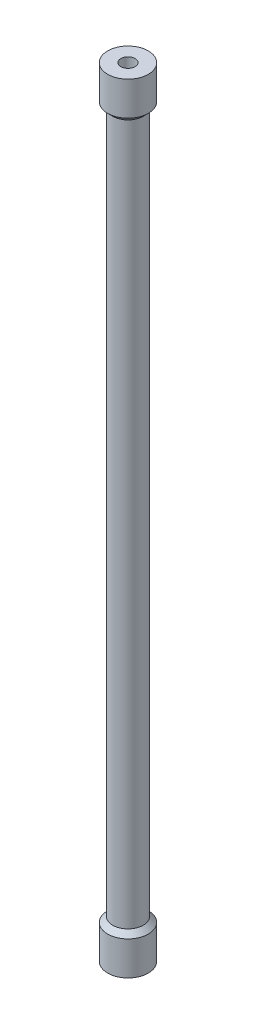
SolidWorks part; units mm, degrees
ref_plane "前视基准面" through (0, 0, 0) normal (0, 0, 1) x (1, 0, 0)
ref_plane "上视基准面" through (0, 0, 0) normal (0, 1, 0) x (1, 0, 0)
ref_plane "右视基准面" through (0, 0, 0) normal (1, 0, 0) x (0, 0, -1)
sketch "草图1" plane through (0, 0, 0) normal (0, 1, 0) x (1, 0, 0)
  circle A0 centre (0, 0) radius 6
  dimension "D1" = 12
extrude "凸台-拉伸1" add sketch "草图1" along normal mid plane 230
sketch "草图2" plane through (0, 0, 0) normal (0, 0, 1) x (1, 0, 0)
  line L0 (6, 105) -> (4.5, 105)
  line L1 (6, -115) -> (6, 115) construction
  line L2 (4.5, 105) -> (4.5, -105)
  line L3 (4.5, -105) -> (6, -105)
  line L4 (6, -105) -> (6, 105)
  line L5 (6, 115) -> (-6, 115) construction
  line L6 (-6, -115) -> (6, -115) construction
  dimension "D1" = 10
  dimension "D2" = 10
  dimension "D3" = 1.5
revolve "切除-旋转1" cut sketch "草图2" angle 360 about axis through (0, 115, 0) along (0, -1, 0)
chamfer "倒角1" distance 1.5 angle 45 2 edges at (0, -105, 4.5) (0, 105, 4.5)
hole_wizard "M5 螺纹孔1" positions "草图4" profile "草图3" tap size "M5" standard "GB"
sketch "草图4" plane through (0, -115, 0) normal (0, -1, 0) x (-1, 0, 0)
  point P0 (0, 0)
sketch "草图3" plane through (0, -115, 0) normal (1, 0, 0) x (0, 0, -1)
  line L0 (0, 0) -> (0, 18.6618)
  line L1 (0, 18.6618) -> (2.1, 17.4)
  line L2 (2.1, 17.4) -> (2.1, 0)
  line L5 (2.1, 0) -> (0, 0)
  line L10 (0, 18.6618) -> (-2.1, 17.4) construction
  line L11 (0, -6.35) -> (0, 107.95) construction
  dimension "螺纹孔钻头直径" = 4.2
  dimension "螺纹孔钻头深度" = 17.4
  dimension "导头角度" = 118
cosmetic thread "孔螺蚊线1" parameters "D1"=15, "D2"=5
mirror "镜向1" about plane through (0, 0, 0) normal (0, 1, 0) of "M5 螺纹孔1"
